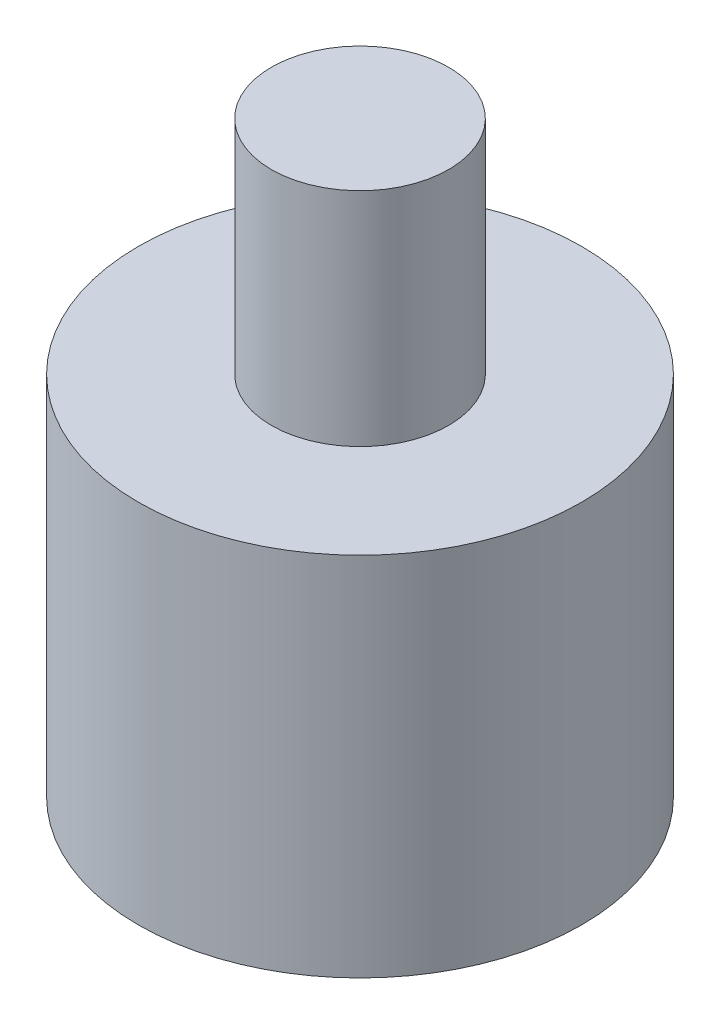
SolidWorks part; units mm, degrees
ref_plane "前视基准面" through (0, 0, 0) normal (0, 0, 1) x (1, 0, 0)
ref_plane "上视基准面" through (0, 0, 0) normal (0, 1, 0) x (1, 0, 0)
ref_plane "右视基准面" through (0, 0, 0) normal (1, 0, 0) x (0, 0, -1)
sketch "草图1" plane through (0, 0, 0) normal (0, 1, 0) x (1, 0, 0)
  circle A0 centre (0, 0) radius 100
extrude "凸台-拉伸1" add sketch "草图1" along normal blind 165.2
ref_plane "基准面5" through (0, 215.2, 0) normal (0, 1, 0) x (1, 0, 0)
sketch "草图3" plane through (0, 215.2, 0) normal (0, 1, 0) x (1, 0, 0)
  circle A0 centre (0, 0) radius 40
extrude "凸台-拉伸3" add sketch "草图3" along normal mid plane 100 separate body contours A0
ref_axis "基准轴1" through (-110, 0, 0) along (1, 0, 0)
